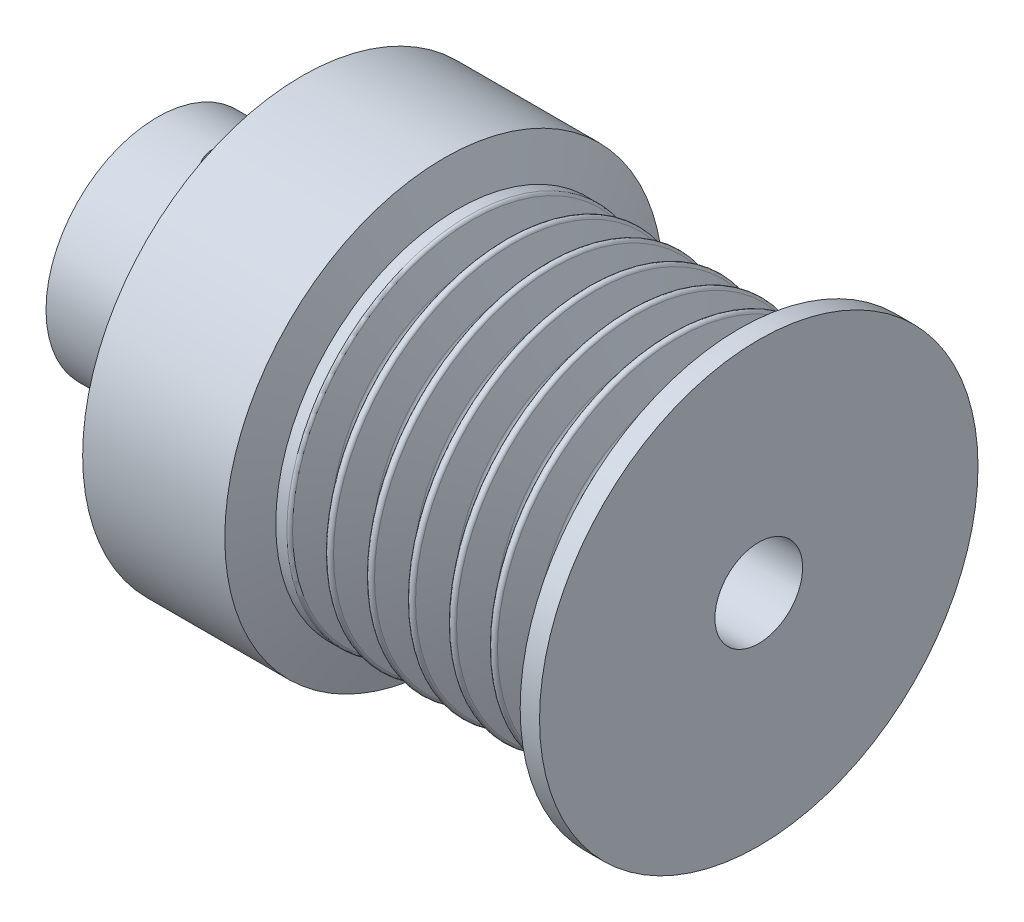
SolidWorks part; units mm, degrees
material "6061-T6 (SS)"
ref_plane "Front Plane" through (0, 0, 0) normal (0, 0, 1) x (1, 0, 0)
ref_plane "Top Plane" through (0, 0, 0) normal (0, 1, 0) x (1, 0, 0)
ref_plane "Right Plane" through (0, 0, 0) normal (1, 0, 0) x (0, 0, -1)
sketch "Sketch1" plane through (0, 0, 0) normal (0, 0, 1) x (1, 0, 0)
  line L0 (0, 0) -> (0, 2.5) construction
  line L1 (0, 2.5) -> (34.29, 2.5)
  line L2 (34.29, 2.5) -> (34.29, 12.5)
  line L3 (34.29, 12.5) -> (8.24, 12.5)
  line L4 (8.24, 12.5) -> (8.24, 6.35)
  line L5 (0, 0) -> (13.5959, 0) construction
  line L8 (8.24, 6.35) -> (0, 6.35)
  line L9 (0, 6.35) -> (0, 2.5)
  dimension "D1" = 25
  dimension "D2" = 5
  dimension "D3" = 26.05
  dimension "D6" = 12.7
  dimension "D7" = 8.24
revolve "Revolve1" add sketch "Sketch1" angle 360 about L5
sketch "Sketch2" plane through (0, 0, 0) normal (0, 0, 1) x (1, 0, 0)
  line L0 (29.4386, 12.5) -> (29.4386, 10.3699)
  line L2 (29.6295, 10.2362) -> (30.2251, 8.5999)
  line L3 (30.9889, 8.5999) -> (31.5845, 10.2362)
  line L4 (31.7754, 10.3699) -> (31.7754, 12.5)
  line L5 (31.7754, 12.5) -> (29.4386, 12.5)
  line L6 (29.4386, 11.43) -> (31.7754, 11.43) construction
  line L7 (15.24, 0) -> (34.29, 0) construction
  line L8 (29.6295, 10.2362) -> (31.5845, 10.2362) construction
  line L9 (29.4386, 12.5) -> (27.1018, 12.5) construction
  line L10 (34.29, 12.5) -> (8.24, 12.5) construction
  line L11 (27.1018, 12.5) -> (24.765, 12.5) construction
  line L13 (24.765, 0) -> (24.765, 12.5) construction
  line L15 (34.29, -12.5) -> (34.29, 12.5) construction
  line L16 (8.24, 12.5) -> (8.24, -12.5) construction
  arc A0 (29.4386, 10.3699) -> (29.6295, 10.2362) centre (29.4386, 10.1667) cw
  arc A1 (30.2251, 8.5999) -> (30.9889, 8.5999) centre (30.607, 8.7389) ccw
  arc A2 (31.5845, 10.2362) -> (31.7754, 10.3699) centre (31.7754, 10.1667) cw
  point P2 (0, 0)
  point P26 (0, 0)
  point P27 (0, 0)
  dimension "D1" = 0.4064
  dimension "D5" = 0.2032
  dimension "D2" = 2.3368
  dimension "D4" = 1.1938
  dimension "D6" = 40
  dimension "D3" = 7
  dimension "D7" = 11.43
revolve "Cut-Revolve1" cut sketch "Sketch2" angle 360 about L7
pattern_linear "LPattern1" count 6 spacing 2.3368 along (-1, 0, 0) of "Cut-Revolve1"
sketch "Sketch3" plane through (0, 0, 0) normal (0, 0, 1) x (1, 0, 0)
  line L0 (31.7754, 12.5) -> (33.1857, 12.5)
  line L1 (34.29, 12.5) -> (31.7754, 12.5) construction
  line L2 (33.1857, 12.5) -> (32.4104, 10.3699)
  line L3 (32.4104, 10.3699) -> (31.7754, 10.3699)
  line L4 (31.7754, 12.5) -> (31.7754, -12.5) construction
  line L5 (31.7754, 10.3699) -> (31.7754, 12.5)
  line L6 (31.7754, 10.3699) -> (31.7754, -10.3699) construction
  line L7 (30.607, 8.3325) -> (30.607, 11.4458) construction
  line L8 (24.765, 10.3699) -> (24.765, 14.7012) construction
  line L9 (17.7546, 10.3699) -> (17.7546, 12.5)
  line L10 (17.1196, 10.3699) -> (17.7546, 10.3699)
  line L11 (16.3443, 12.5) -> (17.1196, 10.3699)
  line L12 (17.7546, 12.5) -> (16.3443, 12.5)
  line L13 (0, 0) -> (26.9583, 0) construction
  arc A0 (30.2251, 8.5999) -> (30.9889, 8.5999) centre (30.607, 8.7389) ccw construction
  arc A1 (24.9559, 10.2362) -> (24.5741, 10.2362) centre (24.765, 10.1667) ccw construction
  dimension "D1" = 1.8034
  dimension "D2" = 20
revolve "Cut-Revolve2" cut sketch "Sketch3" angle 360 about L13
fillet "Fillet1" radius 0.762 1 edges at (8.24, 0, 6.35)
ref_plane "Plane1" through (0, 6.35, 0) normal (0, 1, 0) x (1, 0, 0)
sketch "Sketch6" plane through (0, 6.35, 0) normal (0, 1, 0) x (1, 0, 0)
  line L1 (5.065, 0) -> (0, 0) construction
  line L6 (8.24, 12.5) -> (8.24, -12.5) construction
  circle A0 centre (5.065, 0) radius 3.175 construction
  point P0 (5.065, 0)
  point P24 (3.5635, 0)
  dimension "D1" = 6.35
hole_wizard "#10-24 Tapped Hole1" positions "Sketch6" profile "Sketch5" tap size "#10-24" standard "ANSI Inch" end condition up to next
sketch "Sketch5" plane through (5.065, 6.35, 0) normal (1, 0, 0) x (0, 0, 1)
  line L0 (0, 0) -> (0, 3.85)
  line L1 (0, 3.85) -> (1.8986, 3.85)
  line L2 (1.8986, 3.85) -> (1.8986, 0)
  line L5 (1.8986, 0) -> (0, 0)
  line L11 (0, -6.35) -> (0, 107.95) construction
  dimension "Thru Tap Drill Dia." = 3.7973
  dimension "Thru Tap Drill Depth" = 3.85
equation "\"D2@Sketch1\"=5mm"
equation "\"D3@Sketch2\"=0.9in/2"
equation "\"D4@Sketch2\"=0.094in/2"
equation "\"D1@Sketch1\"=25mm"
equation "\"D3@Sketch1\"=0.75in+7mm"
equation "\"D7@Sketch2\"=0.9in/2"
equation "\"D7@Sketch1\"=0.60in-7mm"
